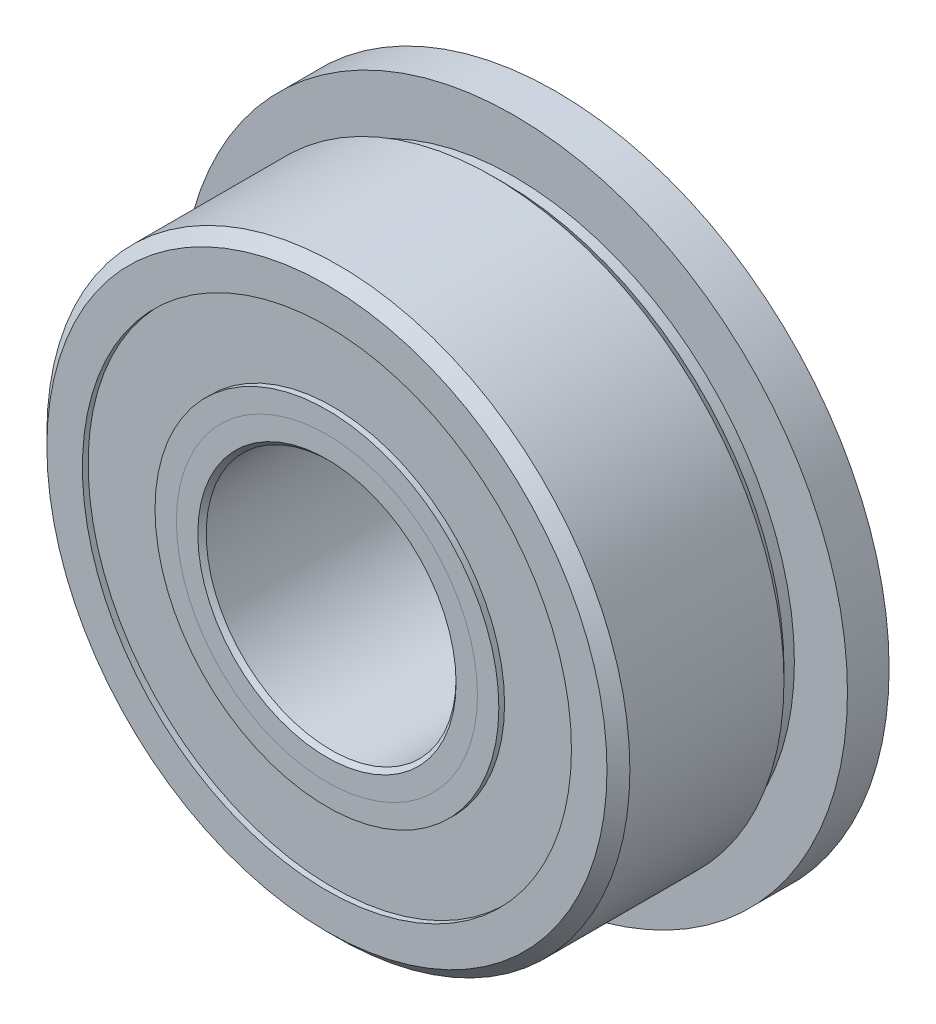
SolidWorks part; units mm, degrees
material "AISI 316 Stainless Steel Sheet (SS)"
ref_plane "Front Plane" through (0, 0, 0) normal (0, 0, 1) x (1, 0, 0)
ref_plane "Top Plane" through (0, 0, 0) normal (0, 1, 0) x (1, 0, 0)
ref_plane "Right Plane" through (0, 0, 0) normal (1, 0, 0) x (0, 0, -1)
sketch "Sketch1" plane through (0, 0, 0) normal (1, 0, 0) x (0, 0, -1)
  line L0 (-4.3656, 0) -> (4.3656, 0) construction
  line L1 (0, 11.1125) -> (0, -11.1125) construction
  line L2 (3.9291, 11.1125) -> (-3.9291, 11.1125) construction
  line L3 (-3.9291, 11.1125) -> (-4.3656, 10.6759) construction
  line L4 (-4.3656, 10.6759) -> (-4.3656, 9.3215) construction
  line L5 (-4.3656, 9.3215) -> (-2.4946, 9.3215) construction
  line L6 (4.3656, 9.3215) -> (2.4946, 9.3215) construction
  line L7 (4.3656, 10.6759) -> (4.3656, 9.3215) construction
  line L8 (3.9291, 11.1125) -> (4.3656, 10.6759) construction
  line L9 (0, 11.1125) -> (0, 7.9375) construction
  line L10 (0, 7.9375) -> (0, 4.7625) construction
  line L11 (4.3656, 0) -> (5.9531, 0) construction
  line L12 (5.9531, 5.9563) -> (5.9531, -5.9563) construction
  line L13 (5.9531, -12.7) -> (5.9531, 12.7) construction
  arc A0 (-2.4946, 9.3215) -> (2.4946, 9.3215) centre (0, 7.9375) cw construction
  point P14 (0, 4.7625)
  point P20 (5.9531, 0)
  point P23 (5.9531, 0)
  dimension "OD" = 22.225
  dimension "D1" = 45
  dimension "D2" = 0.4366
  dimension "D3" = 4.9893
  dimension "D4" = 1.384
  dimension "Width" = 8.7312
  dimension "Total Wd" = 10.3187
  dimension "Shaft Dia" = 9.525
  dimension "Inner Ring OD" = 11.9126
  dimension "Flange OD" = 25.4
sketch "Sketch11" plane through (0, 0, 0) normal (0, 0, 1) x (1, 0, 0)
  circle A0 centre (0, 0) radius 4.7625 construction
  dimension "Shaft Dia" = 9.525
sketch "Sketch8" plane through (0, 0, 0) normal (1, 0, 0) x (0, 0, -1)
  line L0 (3.9291, 11.1125) -> (-3.9291, 11.1125) construction
  line L1 (3.9291, 11.1125) -> (4.3656, 10.6759) construction
  line L2 (4.3656, 10.6759) -> (4.3656, 9.3215) construction
  line L3 (4.3656, 9.3215) -> (2.4946, 9.3215) construction
  line L4 (-4.3656, 9.3215) -> (-2.4946, 9.3215) construction
  line L5 (-4.3656, 10.6759) -> (-4.3656, 9.3215) construction
  line L6 (-3.9291, 11.1125) -> (-4.3656, 10.6759) construction
  line L7 (3.9291, 11.1125) -> (-3.9291, 11.1125)
  line L8 (3.9291, 11.1125) -> (4.3656, 10.6759)
  line L9 (4.3656, 10.6759) -> (4.3656, 9.3215)
  line L10 (4.3656, 9.3215) -> (2.4946, 9.3215)
  line L11 (-4.3656, 9.3215) -> (-2.4946, 9.3215)
  line L12 (-4.3656, 10.6759) -> (-4.3656, 9.3215)
  line L13 (-3.9291, 11.1125) -> (-4.3656, 10.6759)
  arc A0 (2.4946, 9.3215) -> (-2.4946, 9.3215) centre (0, 7.9375) ccw construction
  arc A1 (2.4946, 9.3215) -> (-2.4946, 9.3215) centre (0, 7.9375) ccw
revolve "Revolve7" add sketch "Sketch8" angle 360 about L0 region at (0, 10.8312, -4.0843)
sketch "Sketch2" plane through (0, 0, 0) normal (1, 0, 0) x (0, 0, -1)
  line L0 (-4.3656, 6.5535) -> (-2.4946, 6.5535)
  line L2 (-4.3656, 6.5535) -> (-4.3656, 5.7386)
  line L3 (-4.3656, 5.7386) -> (-3.5507, 4.9236)
  line L4 (-3.5507, 4.9236) -> (0, 4.9236)
  line L5 (0, 11.1125) -> (0, -11.1125) construction
  line L6 (0, 4.9236) -> (0, 5.0847)
  line L7 (0, 5.0847) -> (0, 4.7625) construction
  line L8 (-4.3656, 6.5535) -> (-4.3656, 4.9236) construction
  line L9 (-4.3656, 4.9236) -> (-3.5507, 4.9236) construction
  line L10 (-4.3656, 10.6759) -> (-4.3656, -10.6759) construction
  arc A0 (-2.4946, 6.5535) -> (0, 5.0847) centre (0, 7.9375) ccw
  arc A1 (2.4946, 9.3215) -> (-2.4946, 9.3215) centre (0, 7.9375) ccw construction
  circle A2 centre (0, 7.9375) radius 2.8528 construction
  dimension "D1" = 45
revolve "Revolve2" add sketch "Sketch2" angle 360 about L0
sketch "Sketch3" plane through (0, 0, 0) normal (1, 0, 0) x (0, 0, -1)
  line L0 (-4.3656, 5.7386) -> (-3.5507, 4.9236)
  line L1 (-3.5507, 4.9236) -> (0, 4.9236)
  line L2 (0, 4.9236) -> (0, 5.0847)
  line L3 (-4.3656, 5.7386) -> (-4.3656, 4.9236)
  line L4 (-4.3656, 6.5535) -> (-4.3656, 4.9236) construction
  line L5 (-4.3656, 4.9236) -> (-4.2045, 4.7625)
  line L6 (-4.2045, 4.7625) -> (5.5166, 4.7625)
  line L7 (10.4392, 0) -> (-10.4392, 0) construction
  line L8 (5.5166, 4.7625) -> (5.9531, 5.1991)
  line L10 (5.9531, 5.1991) -> (5.9531, 5.9563)
  line L11 (5.9531, 5.9563) -> (2.0527, 5.9563)
  line L13 (3.9291, 11.1125) -> (4.3656, 10.6759) construction
  circle A0 centre (0, 7.9375) radius 2.8528 construction
  arc A1 (2.0527, 5.9563) -> (0, 5.0847) centre (0, 7.9375) cw
  point P18 (0, 0)
  dimension "Inner Ring OD" = 11.9126
revolve "Revolve3" add sketch "Sketch3" angle 360 about L0
sketch "Sketch5" plane through (0, 0, 0) normal (1, 0, 0) x (0, 0, -1)
  line L0 (4.3656, 10.6759) -> (4.3656, 9.3215) construction
  line L1 (4.3656, 9.9987) -> (2.7781, 9.9987)
  line L2 (4.3656, 9.9987) -> (4.3656, 12.7)
  line L3 (4.3656, 12.7) -> (2.7781, 12.7)
  line L4 (2.7781, 9.9987) -> (2.7781, 12.7)
  line L5 (5.9531, 0) -> (-4.3656, 0) construction
  dimension "Flange OD" = 25.4
  dimension "D1" = 1.5875
revolve "Revolve5" add sketch "Sketch5" angle 360 about L5
sketch "Sketch6" plane through (0, 0, 0) normal (1, 0, 0) x (0, 0, -1)
  line L0 (1.9447, 11.1125) -> (2.3813, 10.6759)
  line L1 (3.9291, 11.1125) -> (-3.9291, 11.1125) construction
  line L2 (2.3813, 10.6759) -> (2.7781, 10.6759)
  line L3 (2.7781, 10.6759) -> (2.7781, 11.1125)
  line L4 (2.7781, 11.1125) -> (1.9447, 11.1125)
  line L5 (3.9291, 11.1125) -> (4.3656, 10.6759) construction
  line L6 (2.7781, 9.9987) -> (2.7781, 12.7) construction
  dimension "D1" = 0.3969
revolve "Cut-Revolve1" cut sketch "Sketch6" angle 360 about L0
sketch "Sketch4" plane through (0, 0, 0) normal (1, 0, 0) x (0, 0, -1)
  line L0 (-2.8528, 7.9375) -> (2.8528, 7.9375)
  circle A1 centre (0, 7.9375) radius 2.8528 construction
  arc A2 (-2.8528, 7.9375) -> (2.8528, 7.9375) centre (0, 7.9375) cw
  arc A3 (2.4946, 9.3215) -> (-2.4946, 9.3215) centre (0, 7.9375) ccw construction
revolve "Revolve4" add sketch "Sketch4" angle 360 about L0
ref_axis "Axis1" through (0, 0, -4.3656) along (0, 0, 1)
pattern_circular "CirPattern1" count 12 over 360 about axis through (0, 0, 4.3656) along (0, 0, -1) of bodies 104
sketch "Sketch7" plane through (0, 0, 0) normal (1, 0, 0) x (0, 0, -1)
  line L0 (-4.3656, 9.3215) -> (-2.4946, 9.3215) construction
  line L1 (-4.1473, 9.3215) -> (-2.8528, 9.3215)
  line L2 (-4.1473, 9.3215) -> (-4.1473, 6.5535)
  line L3 (-4.1473, 6.5535) -> (-2.8528, 6.5535)
  line L4 (-2.8528, 9.3215) -> (-2.8528, 6.5535)
  line L5 (-4.3656, 6.5535) -> (-2.4946, 6.5535) construction
  line L6 (-3.9291, 11.1125) -> (-4.3656, 10.6759) construction
  line L7 (4.3656, 9.3215) -> (2.4946, 9.3215) construction
  line L8 (4.1473, 9.3215) -> (2.8528, 9.3215)
  line L9 (4.1473, 9.3215) -> (4.1473, 5.9563)
  line L10 (4.1473, 5.9563) -> (2.8528, 5.9563)
  line L11 (2.8528, 9.3215) -> (2.8528, 5.9563)
  line L12 (5.9531, 5.9563) -> (2.0527, 5.9563) construction
  line L13 (3.9291, 11.1125) -> (4.3656, 10.6759) construction
  circle A0 centre (0, 7.9375) radius 2.8528 construction
  point P10 (-4.1473, 10.8942)
  point P21 (4.1473, 10.8942)
revolve "Revolve6" add sketch "Sketch7" angle 360 about L0
sketch "Sketch9" plane through (0, 0, -5.9531) normal (0, 0, -1) x (-1, 0, 0)
  line L0 (0, 5.9563) -> (0, 5.1991) construction
  circle A0 centre (0, 0) radius 5.1991 construction
  circle A1 centre (0, 0) radius 5.9563
  circle A2 centre (0, 0) radius 5.9563 construction
  circle A3 centre (0, 0) radius 5.1991 construction
  circle A4 centre (0, 0) radius 5.5777 construction
  circle A5 centre (0, 0) radius 5.6968
  circle A6 centre (0, 0) radius 5.4586
  point P8 (0, 5.5777)
  dimension "D2" = 0.1191
extrude "Cut-Extrude1" cut sketch "Sketch9" against normal blind 0.127
sketch "Sketch10" plane through (0, 0, -4.1473) normal (0, 0, -1) x (-1, 0, 0)
  circle A0 centre (0, 0) radius 5.9563 construction
  circle A1 centre (0, 0) radius 5.9563
  circle A2 centre (0, 0) radius 6.4328
  dimension "D1" = 0.4765
extrude "Cut-Extrude2" cut sketch "Sketch10" against normal blind 0.254
equation "\"D2@Sketch1\" = \"Width@Sketch1\"*.05"
equation "\"D3@Sketch1\"=\"Width@Sketch1\"/1.75"
equation "\"D4@Sketch1\"=(((\"OD@Sketch1\"-\"Width@Sketch1\")/2)/3.25)/1.5"
equation "\"Inner Ring OD@Sketch3\"=\"Inner Ring OD@Sketch1\""
equation "\"Flange OD@Sketch5\"=\"Flange OD@Sketch1\""
equation "\"D1@Sketch10\"=\"Inner Ring OD@Sketch1\"*.04"
equation "\"D2@Sketch9\"=\"Inner Ring OD@Sketch1\"*.01"
equation "\"D3@Sketch9\"=\"Inner Ring OD@Sketch1\"*.01"
equation "\"Shaft Dia@Sketch1\"=\"Shaft Dia@Sketch11\""
